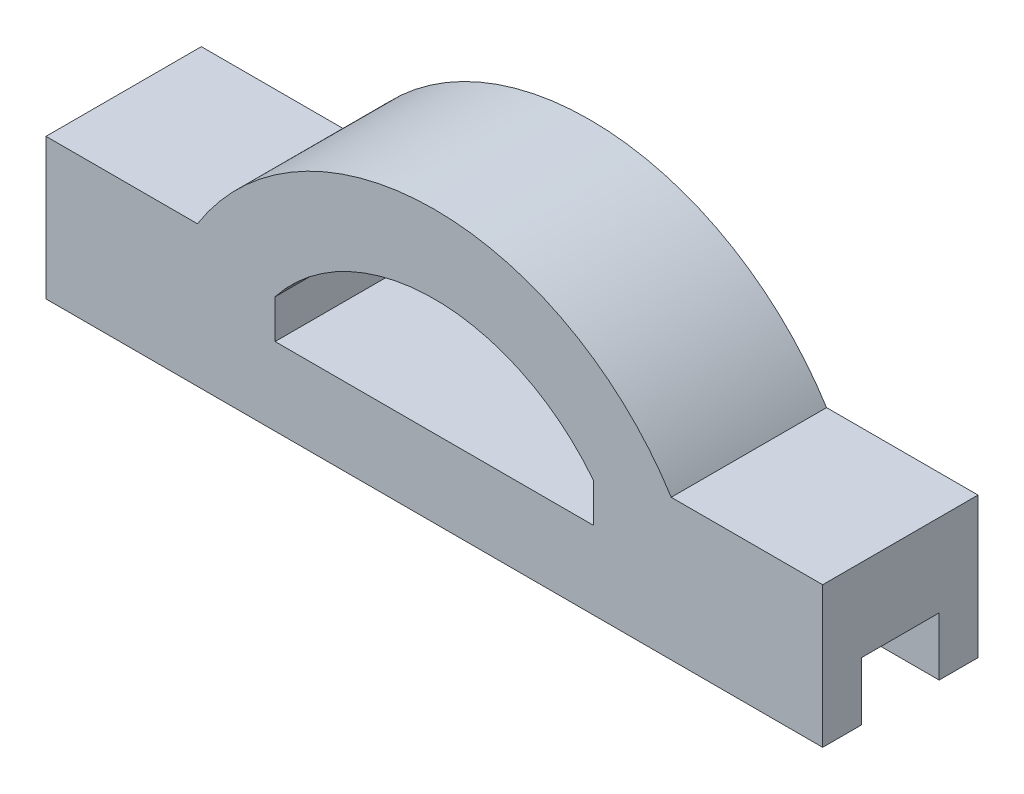
SolidWorks part; units mm, degrees
ref_plane "Front Plane" through (0, 0, 0) normal (0, 0, 1) x (1, 0, 0)
ref_plane "Top Plane" through (0, 0, 0) normal (0, 1, 0) x (1, 0, 0)
ref_plane "Right Plane" through (0, 0, 0) normal (1, 0, 0) x (0, 0, -1)
sketch "Sketch1" plane through (0, 0, 0) normal (0, 0, 1) x (1, 0, 0)
  line L6 (0, 0) -> (20, 0)
  line L12 (0, 2) -> (0, 0)
  line L13 (5.9, 2) -> (5.9, 3)
  line L14 (14.1, 2) -> (14.1, 3)
  line L19 (5.9, 2) -> (14.1, 2)
  line L21 (10, 2) -> (10, 9.0461) construction
  line L23 (0, 3.6271) -> (0, 2)
  line L25 (3.9, 2) -> (3.9, 3.6271) construction
  line L27 (20, 0) -> (20, 3.6271)
  line L28 (16.1, 2) -> (16.1, 3.6271) construction
  line L29 (0, 3.6271) -> (3.9, 3.6271)
  line L30 (16.1, 3.6271) -> (20, 3.6271)
  line L31 (0, 2) -> (5.9, 2) construction
  line L32 (14.1, 2) -> (20, 2) construction
  arc A4 (14.1, 3) -> (5.9, 3) centre (10, -0.2025) ccw
  arc A5 (16.1, 3.6271) -> (3.9, 3.6271) centre (10, -0.2025) ccw
  point P18 (10, 5)
  dimension "D1" = 20
  dimension "D2" = 2
  dimension "D4" = 1
  dimension "D5" = 3
  dimension "D3" = 8.2
  dimension "D6" = 2
extrude "Boss-Extrude1" add sketch "Sketch1" along normal blind 2 and the other way blind 2
sketch "Sketch2" plane through (0, 0, 0) normal (-1, 0, 0) x (0, 0, 1)
  line L0 (0, 0) -> (0, 3.6271) construction
  line L7 (-2, 3.6271) -> (2, 3.6271) construction
  line L8 (-1, 0) -> (1, 0)
  line L9 (-2, 0) -> (2, 0) construction
  line L10 (1, 0) -> (1, 1.5)
  line L11 (1, 1.5) -> (-1, 1.5)
  line L12 (-1, 0) -> (-1, 1.5)
  point P12 (0, 1.5)
  dimension "D1" = 1
  dimension "D2" = 1.5
extrude "Cut-Extrude1" cut sketch "Sketch2" against normal blind 2
ref_plane "Plane1" through (10, 0, 0) normal (-1, 0, 0) x (0, 0, 1)
mirror "Mirror1" about plane through (10, 0, 0) normal (-1, 0, 0) of "Cut-Extrude1"
